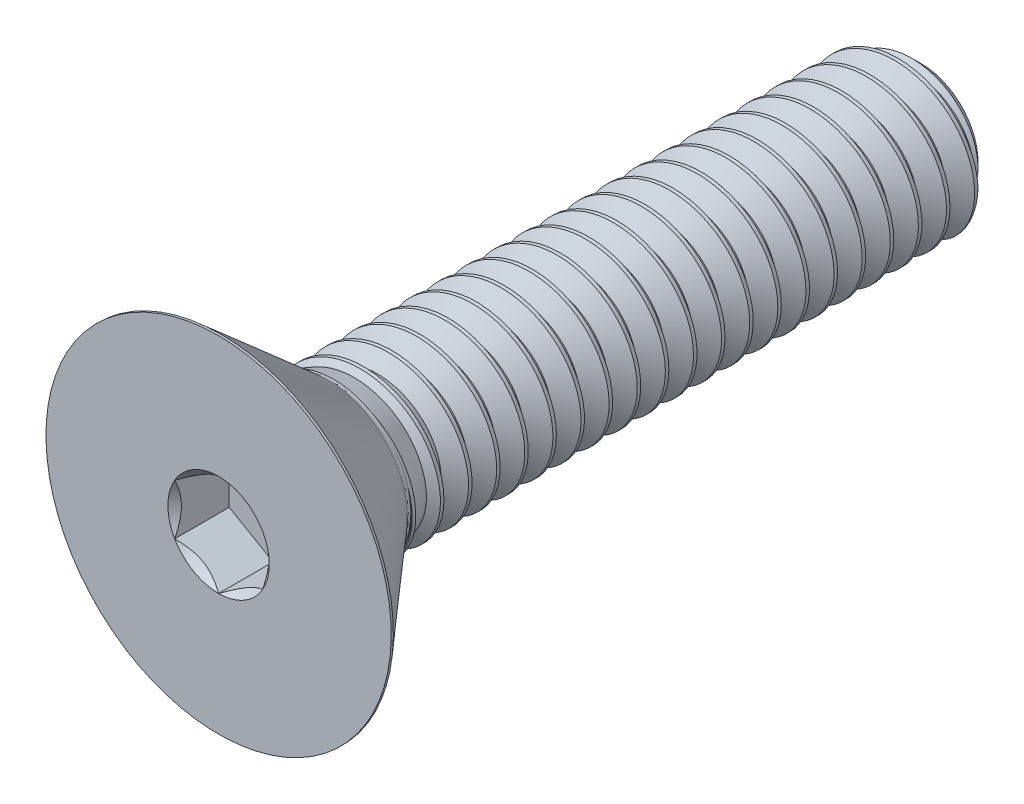
SolidWorks part; units mm, degrees
ref_plane "Front Plane" through (0, 0, 0) normal (0, 0, 1) x (1, 0, 0)
ref_plane "Top Plane" through (0, 0, 0) normal (0, 1, 0) x (1, 0, 0)
ref_plane "Right Plane" through (0, 0, 0) normal (1, 0, 0) x (0, 0, -1)
sketch "Sketch1" plane through (0, 0, 0) normal (1, 0, 0) x (0, 0, -1)
  line L0 (-7.9375, 0) -> (7.9375, 0) construction
  line L1 (-7.9375, 0) -> (-7.9375, 3.8989)
  line L2 (-7.9375, 3.8989) -> (-7.8882, 3.8989)
  line L3 (-7.8882, 3.8989) -> (-5.4737, 1.8)
  line L4 (-7.8882, -3.8989) -> (-5.4737, -1.8)
  line L5 (7.9375, 0) -> (7.9375, 1.7526)
  line L6 (7.9375, 1.7526) -> (-5.4737, 1.7526)
  line L7 (7.4612, 1.7526) -> (7.9375, 1.2763)
  line L8 (7.8978, 1.8213) -> (8.2153, 1.2714) construction
  line L9 (8.2153, 1.2714) -> (8.5328, 1.8213) construction
  line L10 (8.5328, 1.8213) -> (7.8978, 1.8213) construction
  line L11 (7.9177, 1.787) -> (8.513, 1.787)
  line L12 (8.513, 1.787) -> (8.255, 1.3402)
  line L13 (8.255, 1.3402) -> (8.1756, 1.3402)
  line L14 (8.1756, 1.3402) -> (7.9177, 1.787)
  line L15 (8.2153, 1.3402) -> (8.2153, 1.2714) construction
  line L16 (7.9375, 1.7526) -> (8.4931, 1.7526) construction
  line L17 (8.2153, 1.8213) -> (8.2153, 1.7526) construction
  line L18 (7.9375, -1.7526) -> (-5.4737, -1.7526)
  arc A0 (-5.4737, 1.8) -> (-5.347, 1.7526) centre (-5.347, 1.9458) ccw
  point P2 (0, 0)
  point P23 (-6.7056, 0)
  point P27 (8.2153, 1.787)
  point P30 (6.985, -1.7526)
  point P31 (-5.4737, 3.8989)
  point P34 (-7.8882, -3.8989)
  dimension "Length" = 15.875
  dimension "Head Height" = 2.4638
  dimension "Head Diameter" = 7.7978
  dimension "Countersink Angle" = 82
  dimension "Screw Size Decimal Equivalent" = 3.5052
  dimension "Pitch" = 0.635
  dimension "D4" = 0.0794
  dimension "D3" = 45
  dimension "D5" = 0.4763
  dimension "D6" = 1.2319
  dimension "D1" = 0.9525
  dimension "D7" = 0.0493
sketch "Sketch8" plane through (0, 0, 0) normal (0, 0, 1) x (1, 0, 0)
  line L1 (0, 1.1457) -> (-0.9922, 0.5728)
  line L2 (-0.9922, 0.5728) -> (-0.9922, -0.5728)
  line L3 (-0.9922, -0.5728) -> (0, -1.1457)
  line L4 (0, -1.1457) -> (0.9922, -0.5728)
  line L5 (0.9922, -0.5728) -> (0.9922, 0.5728)
  line L6 (0.9922, 0.5728) -> (0, 1.1457)
  circle A0 centre (0, 0) radius 0.9922 construction
  dimension "Drive Size" = 1.9844
sketch "Sketch2" plane through (0, 0, 0) normal (1, 0, 0) x (0, 0, -1)
  line L0 (-7.8882, 3.8989) -> (-5.4737, 1.8) construction
  line L1 (-7.9375, 0) -> (-7.9375, 3.8989) construction
  line L2 (-7.8882, 3.8989) -> (-5.4737, 1.8)
  line L3 (-7.9375, 0) -> (-7.9375, 3.8989)
  line L4 (-7.9375, 3.8989) -> (-7.8882, 3.8989) construction
  line L5 (-7.9375, 3.8989) -> (-7.8882, 3.8989)
  line L6 (-5.347, 1.7526) -> (7.4612, 1.7526)
  line L7 (7.4612, 1.7526) -> (7.9375, 1.2763)
  line L8 (7.9375, 1.2763) -> (7.9375, 0)
  line L9 (7.9375, 0) -> (-7.9375, 0)
  arc A0 (-5.4737, 1.8) -> (-5.347, 1.7526) centre (-5.347, 1.9458) ccw construction
  arc A1 (-5.4737, 1.8) -> (-5.347, 1.7526) centre (-5.347, 1.9458) ccw
revolve "Revolve1" add sketch "Sketch2" angle 360 about L9
sketch "Sketch9" plane through (0, 0, 7.9375) normal (0, 0, 1) x (1, 0, 0)
  line L0 (0.9922, -0.5728) -> (0.9922, 0.5728) construction
  line L1 (0, -1.1457) -> (0.9922, -0.5728) construction
  line L2 (-0.9922, -0.5728) -> (0, -1.1457) construction
  line L3 (-0.9922, 0.5728) -> (-0.9922, -0.5728) construction
  line L4 (0, 1.1457) -> (-0.9922, 0.5728) construction
  line L5 (0.9922, 0.5728) -> (0, 1.1457) construction
  line L6 (0.9922, -0.5728) -> (0.9922, 0.5728)
  line L7 (0, -1.1457) -> (0.9922, -0.5728)
  line L8 (-0.9922, -0.5728) -> (0, -1.1457)
  line L9 (-0.9922, 0.5728) -> (-0.9922, -0.5728)
  line L10 (0, 1.1457) -> (-0.9922, 0.5728)
  line L11 (0.9922, 0.5728) -> (0, 1.1457)
sketch "Sketch10" plane through (0, 0, 7.9375) normal (0, 0, 1) x (1, 0, 0)
  circle A0 centre (0, 0) radius 1.1457
extrude "Cut-Extrude2" cut sketch "Sketch10" against normal up to vertex (1.2319 mm away) draft 45 up to point (0, 0, 6.7056)
extrude "Cut-Extrude1" cut sketch "Sketch9" against normal up to vertex (1.2319 mm away) up to point (0, 0, 6.7056)
ref_plane "Plane1" through (0, 0, 5.347) normal (0, 0, 1) x (1, 0, 0)
split "Split1" trim tools "Plane1" bodies to split 111 resulting bodies 105 106
sketch "Sketch3" plane through (0, 0, -7.9375) normal (0, 0, -1) x (-1, 0, 0)
  circle A0 centre (0, 0) radius 1.7526 construction
  circle A1 centre (0, 0) radius 1.7526
curve "Helix/Spiral1" pitch 0.635 height 15.875 radius 1.7526 centre (0, 0, -7.9375) axis (0, 0, 1) start towards (0, 1, 0)
sketch "Sketch4" plane through (0, 0, 0) normal (1, 0, 0) x (0, 0, -1)
  line L0 (7.9177, 1.787) -> (8.513, 1.787) construction
  line L1 (8.1756, 1.3402) -> (7.9177, 1.787) construction
  line L2 (8.255, 1.3402) -> (8.1756, 1.3402) construction
  line L3 (8.513, 1.787) -> (8.255, 1.3402) construction
  line L4 (7.9177, 1.787) -> (8.513, 1.787)
  line L5 (8.1756, 1.3402) -> (7.9177, 1.787)
  line L6 (8.255, 1.3402) -> (8.1756, 1.3402)
  line L7 (8.513, 1.787) -> (8.255, 1.3402)
sweep "Cut-Sweep1" cut profiles "Sketch4" path "Helix/Spiral1" align with end faces yes
sketch "Sketch7" plane through (0, 0, 5.347) normal (0, 0, 1) x (1, 0, 0)
  circle A0 centre (0, 0) radius 1.7526
extrude "Boss-Extrude2" add sketch "Sketch7" against normal up to next (13.2845 mm away) draft 20
equation "\"D4@Sketch1\" = \"Pitch@Sketch1\" / 8"
equation "\"D5@Sketch1\"=\"Pitch@Sketch1\"*0.75"
equation "\"D4@Helix/Spiral1\"=\"Pitch@Sketch1\""
equation "\"D3@Helix/Spiral1\"=\"Length@Sketch1\""
equation "\"D6@Sketch1\"=\"Head Height@Sketch1\"/2"
equation "\"D1@Sketch1\"=\"Pitch@Sketch1\"*1.5"
equation "\"D7@Sketch1\"=\"Head Height@Sketch1\"*0.02"
